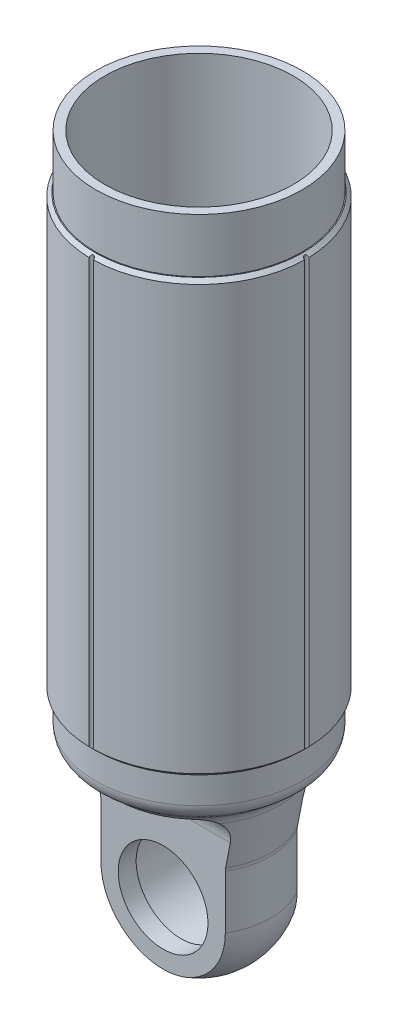
SolidWorks part; units mm, degrees
material "6061 Alloy"
ref_plane "Front" through (0, 0, 0) normal (0, 0, 1) x (1, 0, 0)
ref_plane "Top" through (0, 0, 0) normal (0, 1, 0) x (1, 0, 0)
ref_plane "Right" through (0, 0, 0) normal (1, 0, 0) x (0, 0, -1)
sketch "Sketch1" plane through (0, 0, 0) normal (1, 0, 0) x (0, 0, -1)
  line L0 (0, 0) -> (-18.2563, 0)
  line L1 (-18.2563, 0) -> (-18.2563, -9.525)
  line L2 (-18.2563, -9.525) -> (-18.415, -9.525)
  line L3 (-19.05, -10.16) -> (-19.05, -85.09)
  line L4 (-18.415, -85.725) -> (-18.2562, -85.725)
  line L5 (-18.2562, -85.725) -> (-18.2562, -90.549)
  line L6 (0, 0) -> (0, -127)
  line L7 (-18.415, -9.525) -> (-19.05, -10.16)
  line L8 (-19.05, -85.09) -> (-18.415, -85.725)
  line L9 (-17.0647, -93.0283) -> (-15.2309, -94.4953)
  line L10 (-14.0844, -96.4409) -> (-12.7452, -104.296)
  line L11 (-12.7, -104.8296) -> (-12.7, -114.3)
  arc A0 (-12.7, -114.3) -> (0, -127) centre (0, -114.3) ccw
  arc A1 (-18.2562, -90.549) -> (-17.0647, -93.0283) centre (-15.0812, -90.549) ccw
  arc A2 (-15.2309, -94.4953) -> (-14.0844, -96.4409) centre (-17.2143, -96.9746) cw
  arc A3 (-12.7452, -104.296) -> (-12.7, -104.8296) centre (-15.875, -104.8296) cw
  point P4 (-19.05, -9.525)
  point P5 (-19.05, -85.725)
  point P19 (-18.2562, -92.075)
  point P22 (-14.2875, -95.25)
  dimension "D7" = 25.4
  dimension "D12" = 3.175
  dimension "D1" = 0.7937
  dimension "D2" = 19.05
  dimension "D3" = 9.525
  dimension "D4" = 76.2
  dimension "D5" = 6.35
  dimension "D6" = 14.2875
  dimension "D10" = 114.3
  dimension "D11" = 3.175
revolve "Revolve1" add sketch "Sketch1" angle 360 about L6
sketch "Sketch4" plane through (0, 0, 0) normal (1, 0, 0) x (0, 0, -1)
  line L0 (6.35, -125.2985) -> (6.35, -100.0125)
  line L1 (0, -127) -> (0, -85.09) construction
  line L2 (-19.05, -85.09) -> (19.05, -85.09) construction
  line L3 (-6.35, -125.2985) -> (-6.35, -100.0125)
  line L4 (-12.7, -114.3) -> (12.7, -114.3) construction
  line L5 (11.1125, -95.25) -> (17.4093, -95.25)
  line L6 (17.4093, -95.25) -> (17.4093, -129.2369)
  line L7 (17.4093, -129.2369) -> (-15.9195, -129.2369)
  line L8 (-15.9195, -129.2369) -> (-15.9195, -95.25)
  line L9 (-15.9195, -95.25) -> (-11.1125, -95.25)
  arc A0 (-12.7, -114.3) -> (12.7, -114.3) centre (0, -114.3) ccw construction
  arc A1 (6.35, -100.0125) -> (11.1125, -95.25) centre (11.1125, -100.0125) cw
  arc A2 (-6.35, -100.0125) -> (-11.1125, -95.25) centre (-11.1125, -100.0125) ccw
  point P19 (6.35, -95.25)
  point P22 (-6.35, -95.25)
  dimension "D3" = 4.7625
  dimension "D1" = 12.7
  dimension "D2" = 19.05
extrude "Extrude1" cut sketch "Sketch4" against normal through all and the other way through all
sketch "Sketch5" plane through (0, 0, 6.35) normal (0, 0, 1) x (1, 0, 0)
  circle A0 centre (0, -114.3) radius 7.9375
  arc A1 (-10.9985, -114.3) -> (10.9985, -114.3) centre (0, -114.3) ccw construction
  dimension "D1" = 15.875
extrude "Extrude2" cut sketch "Sketch5" against normal through all
ref_plane "Plane1" through (0, 0, 3.175) normal (0, 0, 1) x (1, 0, 0)
sketch "Sketch6" plane through (0, 0, 3.175) normal (0, 0, 1) x (1, 0, 0)
  circle A0 centre (0, -114.3) radius 9.525
  circle A1 centre (0, -114.3) radius 7.9375 construction
  dimension "D1" = 19.05
extrude "Extrude3" cut sketch "Sketch6" against normal through all
sketch "Sketch7" plane through (0, 0, 0) normal (0, 1, 0) x (-1, 0, 0)
  circle A0 centre (0, 0) radius 16.6688
  circle A1 centre (0, 0) radius 18.2563 construction
  dimension "D1" = 1.5875
extrude "Extrude6" cut sketch "Sketch7" against normal offset from surface (89.279 mm away) 3.175
hole_wizard "1/2-20 Tapped Hole1" positions "3DSketch1" profile "Sketch9" tap size "1/2-20" standard "Ansi Inch"
sketch3d "3DSketch1"
  point P0 (-13.3858, -100.5386, 0)
  dimension "D1" = 6.35
sketch "Sketch9" plane through (-13.3858, -100.5386, 0) normal (0, 0, 1) x (0.1681, -0.9858, 0)
  line L0 (0, 0) -> (0, 22.5076)
  line L1 (0, 22.5076) -> (5.7544, 19.05)
  line L2 (5.7544, 19.05) -> (5.7544, 0)
  line L5 (5.7544, 0) -> (0, 0)
  line L10 (0, 22.5076) -> (-5.7544, 19.05) construction
  line L11 (0, -6.35) -> (0, 107.95) construction
  dimension "Tap Drill Dia." = 11.5087
  dimension "Tap Drill Depth" = 19.05
  dimension "Drill Angle" = 118
ref_plane "Plane3" through (-10.8862, -1.8561, 0) normal (-0.9858, -0.1681, 0) x (0, 0, 1)
sketch "Sketch14" plane through (-10.8862, -1.8561, 0) normal (-0.9858, -0.1681, 0) x (0, 0, 1)
  circle A0 centre (0, -96.8586) radius 5.7544
  arc A1 (-5.6807, -95.9406) -> (5.6807, -95.9406) centre (0, -96.8586) ccw construction
extrude "Cut-Extrude1" cut sketch "Sketch14" along normal through all
sketch "Sketch10" plane through (0, -9.525, 0) normal (0, 1, 0) x (-1, 0, 0)
  circle A0 centre (0, -19.05) radius 0.3969
  circle A1 centre (0, 0) radius 19.05 construction
  circle A2 centre (-19.05, 0) radius 0.3969
  circle A3 centre (0, 19.05) radius 0.3969
  circle A4 centre (19.05, 0) radius 0.3969
  dimension "D1" = 0.7937
extrude "Extrude7" cut sketch "Sketch10" against normal through all
sketch3d "3DSketch2" [suppressed]
  line L0 (0, 0, 0) -> (0, 47.3995, 0) construction
sketch "Sketch11" plane through (0, 0, 0) normal (1, 0, 0) x (0, 0, -1)
  line L0 (19.0459, -10.16) -> (18.2563, -10.5569)
  line L1 (18.2563, -10.5569) -> (19.0459, -10.9538)
  line L2 (19.0459, -10.16) -> (19.4455, -10.16)
  line L3 (18.2563, -9.525) -> (18.2563, 0) construction
  line L4 (19.4455, -10.16) -> (19.4455, -10.9538)
  line L5 (19.0459, -10.16) -> (19.0459, -85.09) construction
  line L6 (19.4455, -10.9538) -> (19.0459, -10.9538)
  dimension "D1" = 0.7937
revolve "Cut-Revolve2" [suppressed] cut sketch "Sketch11" angle 360 about L0
pattern_linear "LPattern1" [suppressed] count 95 spacing 0.7937
sketch3d "3DSketch3"
  line L0 (0, -114.3, 6.35) -> (0, -114.3, -6.35) construction
  line L1 (0, -114.3, 3.175) -> (0, -114.3, 6.35) construction
  line L2 (0, -114.3, -6.35) -> (0, -114.3, 3.175) construction
  point P6 (0, -114.3, 0)
